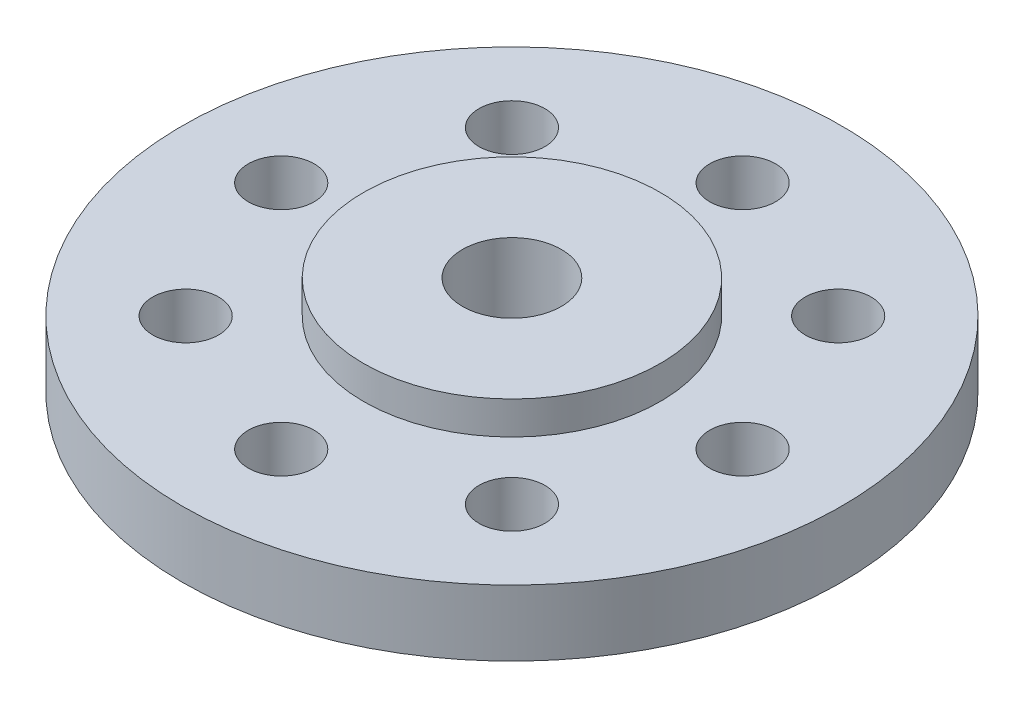
SolidWorks part; units mm, degrees
ref_plane "Front" through (0, 0, 0) normal (0, 0, 1) x (1, 0, 0)
ref_plane "Top" through (0, 0, 0) normal (0, 1, 0) x (1, 0, 0)
ref_plane "Right" through (0, 0, 0) normal (1, 0, 0) x (0, 0, -1)
sketch "Эскиз1" plane through (0, 0, 0) normal (0, 1, 0) x (1, 0, 0)
  circle A0 centre (0, 0) radius 4.5
  circle A1 centre (0, 0) radius 10
extrude "Бобышка-Вытянуть1" add sketch "Эскиз1" along normal blind 1 contours A0 region at (0, 0, 0)
extrude "Бобышка-Вытянуть2" add sketch "Эскиз1<3>" along normal blind 2 from offset 1 separate body contours A1
sketch "Эскиз1<3>" plane through (0, 0, 0) normal (0, 1, 0) x (1, 0, 0) same geometry as "Эскиз1"
extrude "Бобышка-Вытянуть3" add sketch "Эскиз1<4>" along normal blind 1 from offset 3 contours A0 region at (0, 0, 0)
sketch "Эскиз1<4>" plane through (0, 0, 0) normal (0, 1, 0) x (1, 0, 0) same geometry as "Эскиз1"
sketch "Эскиз2" plane through (0, 0, 0) normal (0, 1, 0) x (1, 0, 0)
  circle A0 centre (0, 0) radius 7 construction
  circle A1 centre (0, 0) radius 1.5
  circle A2 centre (-7, 0) radius 1
  circle A3 centre (-4.9497, 4.9497) radius 1
  circle A4 centre (0, 7) radius 1
  circle A5 centre (4.9497, 4.9497) radius 1
  circle A6 centre (7, 0) radius 1
  circle A7 centre (4.9497, -4.9497) radius 1
  circle A8 centre (0, -7) radius 1
  circle A9 centre (-4.9497, -4.9497) radius 1
  point P23 (0, 0)
  dimension "D1" = 3
  dimension "D2" = 8
extrude "Вырез-Вытянуть1" cut sketch "Эскиз2" along normal through all
